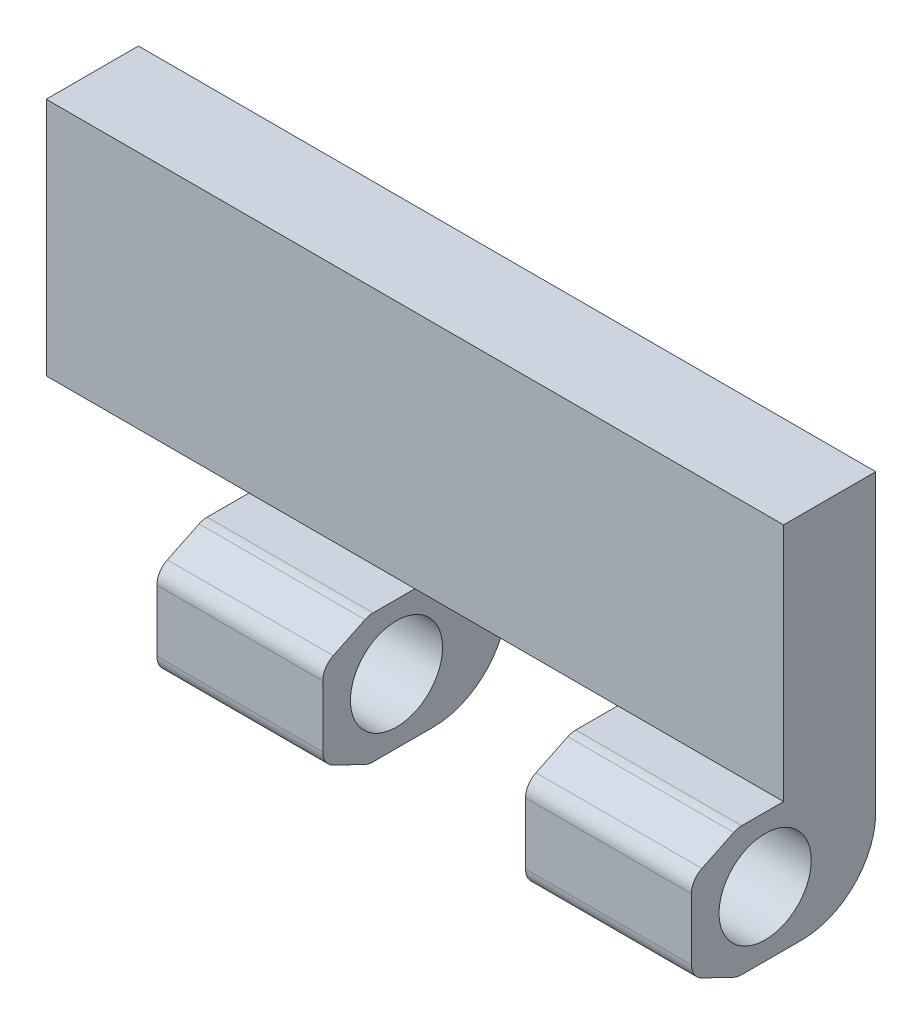
SolidWorks part; units mm, degrees
ref_plane "Front Plane" through (0, 0, 0) normal (1, 0, 0) x (0, 1, 0)
ref_plane "Top Plane" through (0, 0, 0) normal (0, 0, 1) x (0, 1, 0)
ref_plane "Right Plane" through (0, 0, 0) normal (0, 1, 0) x (-1, 0, 0)
sketch "Sketch1" plane through (0, 0, 0) normal (0, 0, 1) x (0, 1, 0)
  line L1 (-6.5, -20) -> (6.5, -20)
  line L2 (-6.5, -20) -> (-6.5, 20)
  line L3 (-6.5, 20) -> (6.5, 20)
  line L4 (6.5, -20) -> (6.5, 20)
  line L5 (-6.5, -20) -> (6.5, 20) construction
  line L6 (-6.5, 20) -> (6.5, -20) construction
  point P0 (0, 0)
  dimension "D1" = 40
  dimension "D2" = 13
extrude "Boss-Extrude1" add sketch "Sketch1" along normal blind 5
sketch "Sketch2" plane through (20, 0, 0) normal (1, 0, 0) x (0, 1, 0)
  line L0 (-6.5, 0) -> (-9.5, 0)
  line L1 (-13.5, 4) -> (-13.5, 7.2724)
  line L2 (-11.6708, 10) -> (-8.3292, 10)
  line L3 (-6.5, 7.2724) -> (-6.5, 5)
  line L4 (-6.5, 5) -> (6.5, 5) construction
  line L5 (6.5, 5) -> (6.5, 0) construction
  line L6 (-6.5985, 7.7052) -> (-7.4277, 9.4327)
  line L7 (-10, 10) -> (-10, 6) construction
  line L8 (-13.4015, 7.7052) -> (-12.5723, 9.4327)
  line L9 (-6.5, 5) -> (-6.5, 0)
  arc A0 (-13.5, 4) -> (-9.5, 0) centre (-9.5, 4) ccw
  circle A1 centre (-10, 6) radius 2.5
  arc A2 (-6.5985, 7.7052) -> (-6.5, 7.2724) centre (-7.5, 7.2724) cw
  arc A3 (-13.4015, 7.7052) -> (-13.5, 7.2724) centre (-12.5, 7.2724) ccw
  arc A4 (-7.4277, 9.4327) -> (-8.3292, 10) centre (-8.3292, 9) ccw
  arc A5 (-12.5723, 9.4327) -> (-11.6708, 10) centre (-11.6708, 9) cw
  point P6 (-6.5, 7.5)
  point P22 (-10, 4.27)
  point P25 (-13.5, 7.5)
  point P28 (-7.7, 10)
  point P31 (-12.3, 10)
  point P32 (-10, 10)
  dimension "D3" = 5
  dimension "D5" = 4
  dimension "D7" = 1
  dimension "D1" = 5
  dimension "D2" = 20
  dimension "D4" = 1.2
  dimension "D6" = 2.5
  dimension "D8" = 4
extrude "Boss-Extrude2" add sketch "Sketch2" against normal blind 9 separate body
pattern_linear "LPattern1" count 2 spacing 20 along (-1, 0, 0) of "Boss-Extrude2"
combine bodies "Combine1" operation type add bodies to combine 102 103 101
